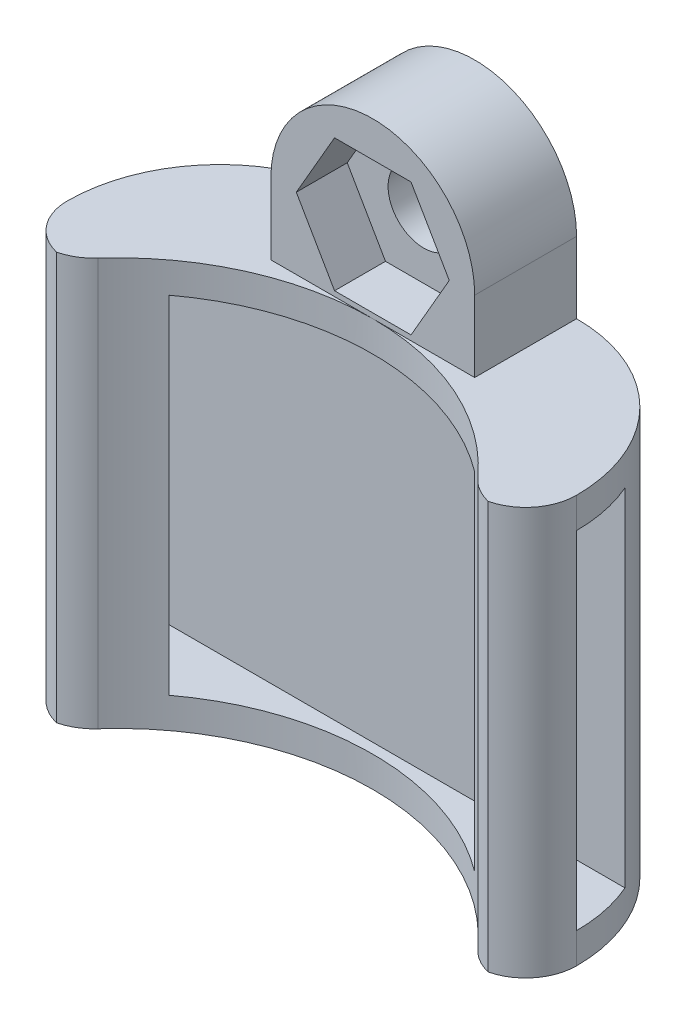
SolidWorks part; units mm, degrees
ref_plane "Plano frontal" through (0, 0, 0) normal (0, 0, 1) x (1, 0, 0)
ref_plane "Plano superior" through (0, 0, 0) normal (0, 1, 0) x (1, 0, 0)
ref_plane "Plano direito" through (0, 0, 0) normal (1, 0, 0) x (0, 0, -1)
sketch "Esboço1" plane through (0, 0, 0) normal (0, 0, 1) x (1, 0, 0)
  line L0 (0, 0) -> (0, -3.5) construction
  line L1 (5, 0) -> (5, -3.5)
  line L2 (-5, 0) -> (-5, -3.5)
  line L3 (-5, -3.5) -> (5, -3.5)
  line L5 (-12.5, -3.5) -> (12.5, -3.5)
  line L6 (-12.5, -3.5) -> (-12.5, -23.5)
  line L7 (-12.5, -23.5) -> (12.5, -23.5)
  line L8 (12.5, -3.5) -> (12.5, -23.5)
  circle A0 centre (0, 0) radius 1.75
  arc A1 (5, 0) -> (-5, 0) centre (0, 0) ccw
  point P3 (0, -3.5)
  point P9 (0, -23.5)
  dimension "D1" = 3.5
  dimension "D2" = 5
  dimension "D3" = 3.5
  dimension "D4" = 20
  dimension "D5" = 25
extrude "Ressalto-extrusão1" add sketch "Esboço1" along normal blind 2.5 contours A0 L5 L1 A1 L2 L3 | L8 L5 L3 L6 L7 region at (4.8688, -1.75, 0) region at (0, -13.5, 0)
sketch "Esboço3" plane through (0, -23.5, 0) normal (0, -1, 0) x (1, 0, 0)
  line L2 (10, 10) -> (12.5, 10)
  line L3 (12.5, 10) -> (12.5, 2.5)
  line L4 (12.5, 2.5) -> (-12.5, 2.5)
  line L5 (-12.5, 2.5) -> (-12.5, 10)
  line L6 (-12.5, 10) -> (-10, 10)
  arc A0 (10, 10) -> (-10, 10) centre (0, 17.5) cw
  point P1 (-16.225, 10)
  point P8 (0, 0)
  point P14 (0, 0)
  line M9 (12.5, 2.5) -> (-12.5, 2.5)
  dimension "D2" = 15
  dimension "D1" = 2.5
  dimension "D3" = 7.5
extrude "Ressalto-extrusão2" add sketch "Esboço3" against normal blind 20 contours L4 A0 L6 L5 | A0 L3 L2 M9 region at (11.25, -23.5, 9.739)
sketch "Esboço4" plane through (-12.5, 0, 0) normal (-1, 0, 0) x (0, 0, 1)
  line L0 (10, -3.5) -> (10, -23.5) construction
  line L1 (4.5, -22) -> (7.5, -22)
  line L2 (4.5, -22) -> (4.5, -5)
  line L3 (4.5, -5) -> (7.5, -5)
  line L4 (7.5, -22) -> (7.5, -5)
  line L5 (10, -3.5) -> (0, -3.5) construction
  line L6 (10, -23.5) -> (0, -23.5) construction
  dimension "D1" = 2.5
  dimension "D2" = 1.5
  dimension "D3" = 1.5
  dimension "D4" = 3
extrude "Corte-extrusão1" cut sketch "Esboço4" against normal blind 39
fillet "Filete1" radius 7.5 2 edges at (-12.5, -13.5, 0) (12.5, -13.5, 0)
fillet "Filete2" radius 2.5 4 edges at (10, -13.5, 10) (-10, -13.5, 10) (12.5, -13.5, 10) (-12.5, -13.5, 10)
sketch "Esboço5" plane through (0, 0, 2.5) normal (0, 0, 1) x (1, 0, 0)
  line L0 (9.3169, -3.5) -> (-9.3169, -3.5) construction
  line L1 (3.7528, 0) -> (1.8764, 3.25)
  line L2 (1.8764, 3.25) -> (-1.8764, 3.25)
  line L3 (-1.8764, 3.25) -> (-3.7528, 0)
  line L4 (-3.7528, 0) -> (-1.8764, -3.25)
  line L5 (-1.8764, -3.25) -> (1.8764, -3.25)
  line L6 (1.8764, -3.25) -> (3.7528, 0)
  line L7 (-5, 0) -> (-5, -5)
  line L8 (-7.5, -5) -> (7.5, -5) construction
  line L9 (-5, -5) -> (5, -5)
  line L10 (11.8739, -5) -> (-11.8739, -5) construction
  line L11 (5, -5) -> (5, 0)
  circle A0 centre (0, 0) radius 3.25 construction
  circle A1 centre (0, 0) radius 5
  line M3 (-5, -3.5) -> (5, -3.5)
  line M4 (5, -3.5) -> (5, 0)
  arc M5 (5, 0) -> (-5, 0) centre (0, 0) ccw
  line M6 (-5, 0) -> (-5, -3.5)
  dimension "D1" = 6.5
extrude "Ressalto-extrusão3" add sketch "Esboço5" along normal blind 2.5 contours A1 M6 M3 | A1 M3 M4 | A1 L9 L11 M3 | A1 L7 L9 M3 | A1 M3 | A1 L6 L5 L4 L3 L2 L1 M5 M3 region at (-4.5842, -2.652, 2.5) region at (0, 4.8688, 2.5) region at (-3.596, -4.3874, 2.5) region at (4.5842, -2.652, 2.5) region at (0, -4.1085, 2.5) region at (3.596, -4.3874, 2.5)
